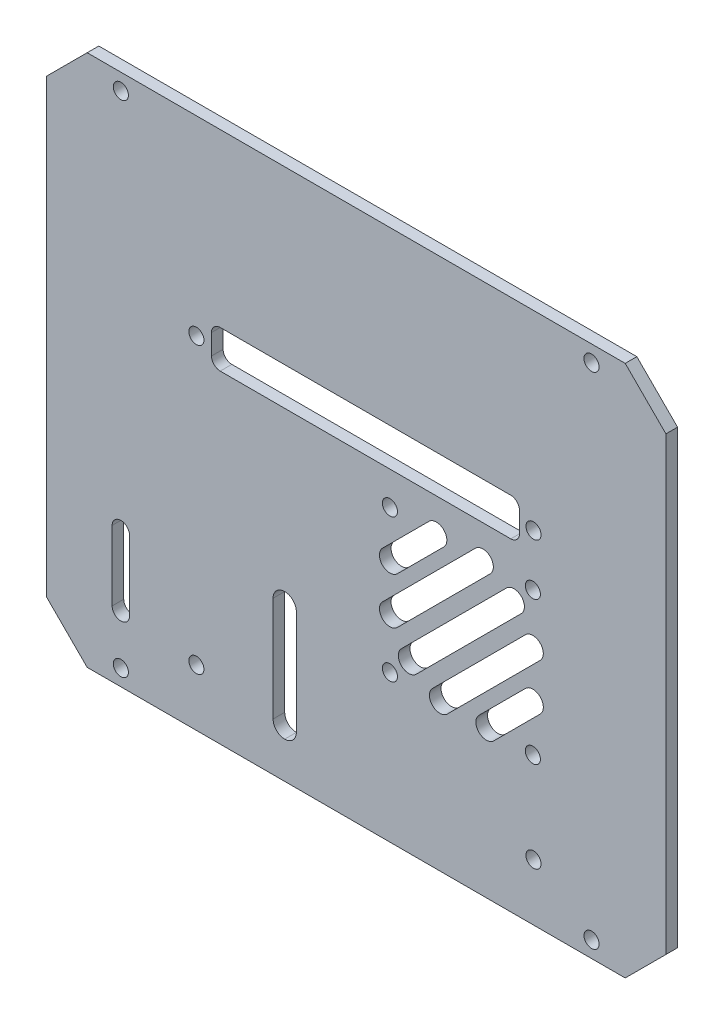
SolidWorks part; units mm, degrees
ref_plane "前视基准面" through (0, 0, 0) normal (0, 0, 1) x (1, 0, 0)
ref_plane "上视基准面" through (0, 0, 0) normal (0, 1, 0) x (1, 0, 0)
ref_plane "右视基准面" through (0, 0, 0) normal (1, 0, 0) x (0, 0, -1)
sketch "草图2" plane through (0, 0, -42.2) normal (0, 0, -1) x (-1, 0, 0)
  line L32 (-57.3467, -34.0538) -> (-50.3426, -41.058)
  line L33 (-50.3426, -41.058) -> (42.2491, -41.058)
  line L34 (42.2491, -41.058) -> (49.2533, -34.0538)
  line L35 (49.2533, -34.0538) -> (49.2533, 43.5378)
  line L36 (49.2533, 43.5378) -> (42.2491, 50.542)
  line L37 (-57.3467, 43.5378) -> (-57.3467, -34.0538)
  line L38 (-50.3426, 50.542) -> (-57.3467, 43.5378)
  line L39 (42.2491, 50.542) -> (-50.3426, 50.542)
  line L40 (-57.3467, -34.0538) -> (-50.3426, -41.058)
  line L41 (-50.3426, -41.058) -> (42.2491, -41.058)
  line L42 (42.2491, -41.058) -> (49.2533, -34.0538)
  line L43 (49.2533, -34.0538) -> (49.2533, 43.5378)
  line L44 (49.2533, 43.5378) -> (42.2491, 50.542)
  line L45 (-57.3467, 43.5378) -> (-57.3467, -34.0538)
  line L46 (-50.3426, 50.542) -> (-57.3467, 43.5378)
  line L47 (42.2491, 50.542) -> (-50.3426, 50.542)
  dimension "D1" = 0.2
extrude "凸台-拉伸1" add sketch "草图2" along normal blind 2
sketch "草图3" plane through (0, 0, -44.2) normal (0, 0, -1) x (-1, 0, 0)
  circle A0 centre (-44.5467, -38.258) radius 1.3
  circle A1 centre (36.4533, -38.258) radius 1.3
  circle A2 centre (-44.5467, 47.742) radius 1.3
  circle A3 centre (36.4533, 47.742) radius 1.3
  circle A4 centre (-44.5467, 47.742) radius 1.15 construction
  circle A5 centre (36.4533, 47.742) radius 1.15 construction
  circle A6 centre (-44.5467, -38.258) radius 1.15 construction
  circle A7 centre (36.4533, -38.258) radius 1.15 construction
  point P2 (-44.5467, 47.742)
  dimension "D1" = 2.6
extrude "切除-拉伸1" cut sketch "草图3" against normal through all
sketch "草图4" plane through (0, 0, -44.2) normal (0, 0, -1) x (-1, 0, 0)
  circle A1 centre (23.4533, -31.2932) radius 1.3
  circle A2 centre (23.4533, -31.2932) radius 1.3
  circle A3 centre (-34.5583, -31.2932) radius 1.3
  circle A4 centre (-34.5583, -31.2932) radius 1.3
  circle A5 centre (23.4533, 17.742) radius 1.3
  circle A6 centre (23.4533, 17.742) radius 1.3
  circle A7 centre (-34.5583, 17.742) radius 1.3
  circle A8 centre (-34.5583, 17.742) radius 1.3
  dimension "D1" = 0
  dimension "D2" = 0
  dimension "D3" = 0
  dimension "D4" = 0
extrude "切除-拉伸2" cut sketch "草图4" against normal up to next
sketch "草图5" plane through (0, 0, -44.2) normal (0, 0, -1) x (-1, 0, 0)
  line L0 (-50.4254, -41.258) -> (42.3319, -41.258) construction
  line L1 (-32.1467, 14.542) -> (20.8533, 14.542)
  line L2 (-32.1467, 14.542) -> (-32.1467, 21.042)
  line L3 (-32.1467, 21.042) -> (20.8533, 21.042)
  line L4 (20.8533, 14.542) -> (20.8533, 21.042)
  line L7 (-57.3467, 43.5378) -> (-57.3467, -34.0538) construction
  dimension "D1" = 53
  dimension "D2" = 6.5
  dimension "D3" = 25.2
  dimension "D4" = 55.8
extrude "切除-拉伸3" cut sketch "草图5" against normal up to next
fillet "圆角1" radius 1.5 4 edges at (32.1467, 21.042, -43.2) (32.1467, 14.542, -43.2) (-20.8533, 14.542, -43.2) (-20.8533, 21.042, -43.2)
sketch "草图7" plane through (0, 0, -44.2) normal (0, 0, -1) x (-1, 0, 0)
  line L0 (-59.0467, 44.242) -> (-59.0467, -34.758) construction
  line L1 (42.9533, 52.242) -> (-51.0467, 52.242) construction
  circle A0 centre (-34.4467, 8.842) radius 1.3
  circle A1 centre (-34.4467, -15.758) radius 1.3
  circle A2 centre (-9.8467, 8.842) radius 1.3
  circle A3 centre (-9.8467, -15.758) radius 1.3
  dimension "D1" = 24.6
  dimension "D2" = 24.6
  dimension "D3" = 24.6
  dimension "D4" = 43.4
extrude "切除-拉伸4" cut sketch "草图7" against normal up to next
sketch "草图8" plane through (0, 0, -44.2) normal (0, 0, -1) x (-1, 0, 0)
  line L0 (-34.4467, 8.842) -> (-9.8467, -15.758) construction
  line L1 (-34.4467, 8.842) -> (-9.8467, 8.842) construction
  line L2 (-34.4467, 8.842) -> (-34.4467, -15.758) construction
  line L3 (-34.4467, -15.758) -> (-9.8467, -15.758) construction
  line L4 (-9.8467, 8.842) -> (-9.8467, -15.758) construction
  line L5 (-31.194, 5.5893) -> (-13.0994, -12.5053) construction
  line L6 (-29.9212, 6.8621) -> (-11.8266, -11.2325)
  line L7 (-32.4668, 4.3165) -> (-14.3722, -13.7781)
  line L8 (-34.4467, 0.242) -> (-18.4467, -15.758) construction
  line L9 (-33.1739, 1.5148) -> (-17.1739, -14.4852)
  line L10 (-35.7195, -1.0308) -> (-19.7195, -17.0308)
  line L11 (-25.8467, 8.842) -> (-9.8467, -7.158) construction
  line L12 (-24.5739, 10.1148) -> (-8.5739, -5.8852)
  line L13 (-27.1195, 7.5692) -> (-11.1195, -8.4308)
  line L14 (-17.8467, 8.842) -> (-9.8467, 0.842) construction
  line L15 (-16.5739, 10.1148) -> (-8.5739, 2.1148)
  line L16 (-19.1195, 7.5692) -> (-11.1195, -0.4308)
  line L17 (-34.4467, -7.758) -> (-26.4467, -15.758) construction
  line L18 (-33.1739, -6.4852) -> (-25.1739, -14.4852)
  line L19 (-35.7195, -9.0308) -> (-27.7195, -17.0308)
  line L20 (42.9533, 52.242) -> (-51.0467, 52.242) construction
  line L22 (-59.0467, 44.242) -> (-59.0467, -34.758) construction
  arc A1 (-29.9212, 6.8621) -> (-32.4668, 4.3165) centre (-31.194, 5.5893) ccw
  arc A2 (-14.3722, -13.7781) -> (-11.8266, -11.2325) centre (-13.0994, -12.5053) ccw
  arc A3 (-33.1739, 1.5148) -> (-35.7195, -1.0308) centre (-34.4467, 0.242) ccw
  arc A4 (-19.7195, -17.0308) -> (-17.1739, -14.4852) centre (-18.4467, -15.758) ccw
  arc A5 (-24.5739, 10.1148) -> (-27.1195, 7.5692) centre (-25.8467, 8.842) ccw
  arc A6 (-11.1195, -8.4308) -> (-8.5739, -5.8852) centre (-9.8467, -7.158) ccw
  arc A7 (-16.5739, 10.1148) -> (-19.1195, 7.5692) centre (-17.8467, 8.842) ccw
  arc A8 (-11.1195, -0.4308) -> (-8.5739, 2.1148) centre (-9.8467, 0.842) ccw
  arc A9 (-33.1739, -6.4852) -> (-35.7195, -9.0308) centre (-34.4467, -7.758) ccw
  arc A10 (-27.7195, -17.0308) -> (-25.1739, -14.4852) centre (-26.4467, -15.758) ccw
  point P10 (-22.1467, -3.458)
  point P15 (-26.4467, -7.758)
  point P22 (-17.8467, 0.842)
  point P29 (-13.8467, 4.842)
  point P36 (-30.4467, -11.758)
  dimension "D1" = 1.8
  dimension "D2" = 1.8
  dimension "D3" = 1.8
  dimension "D4" = 1.8
  dimension "D5" = 1.8
  dimension "D6" = 8
  dimension "D7" = 8
  dimension "D8" = 8
  dimension "D9" = 8
  dimension "D10" = 4.6
  dimension "D11" = 4.6
  dimension "D12" = 43.4
  dimension "D13" = 68
  dimension "D14" = 24.6
extrude "切除-拉伸5" cut sketch "草图8" against normal up to next
sketch "草图9" plane through (0, 0, -44.2) normal (0, 0, -1) x (-1, 0, 0)
  line L0 (49.2533, -34.0538) -> (49.2533, 43.5378) construction
  line L1 (6.2533, -12.758) -> (10.2533, -12.758)
  line L2 (6.2533, -12.758) -> (6.2533, -34.758)
  line L3 (6.2533, -34.758) -> (10.2533, -34.758)
  line L4 (10.2533, -12.758) -> (10.2533, -34.758)
  line L6 (-51.0467, -42.758) -> (42.9533, -42.758) construction
  dimension "D1" = 39
  dimension "D2" = 4
  dimension "D3" = 22
  dimension "D4" = 8
extrude "切除-拉伸6" cut sketch "草图9" against normal blind 8
fillet "圆角2" radius 2 4 edges at (-6.2533, -34.758, -43.2) (-10.2533, -34.758, -43.2) (-10.2533, -12.758, -43.2) (-6.2533, -12.758, -43.2)
sketch "草图10" plane through (0, 0, -44.2) normal (0, 0, -1) x (-1, 0, 0)
  line L0 (23.4533, -31.2932) -> (23.4533, -2.7979) construction
  line L1 (36.4533, -38.258) -> (36.4533, -17.4808) construction
  line L2 (36.4533, -17.758) -> (36.4533, -29.758) construction
  line L3 (37.9533, -17.758) -> (37.9533, -29.758)
  line L4 (34.9533, -17.758) -> (34.9533, -29.758)
  line L5 (50.9533, -34.758) -> (50.9533, 44.242) construction
  line L6 (-51.0467, -42.758) -> (42.9533, -42.758) construction
  arc A0 (37.9533, -17.758) -> (34.9533, -17.758) centre (36.4533, -17.758) ccw
  arc A1 (34.9533, -29.758) -> (37.9533, -29.758) centre (36.4533, -29.758) ccw
  point P8 (36.4533, -23.758)
  dimension "D1" = 1.5
  dimension "D2" = 12
  dimension "D3" = 14.5
  dimension "D4" = 13
extrude "切除-拉伸7" cut sketch "草图10" against normal blind 10
